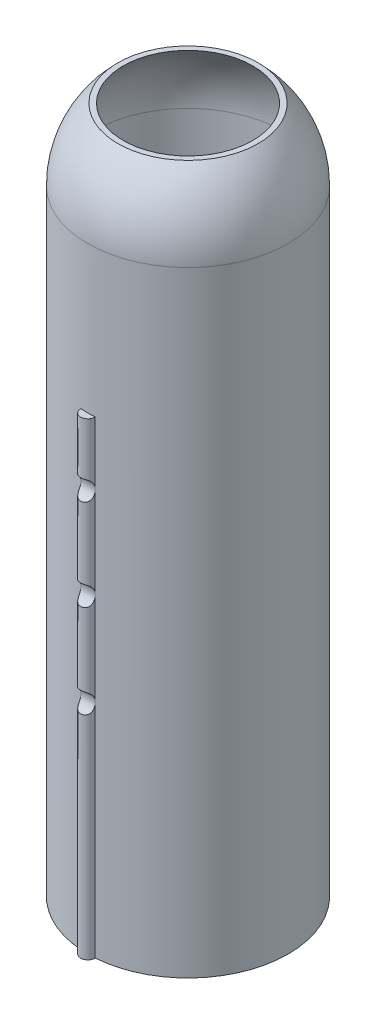
SolidWorks part; units mm, degrees
ref_plane "Front Plane" through (0, 0, 0) normal (0, 0, 1) x (1, 0, 0)
ref_plane "Top Plane" through (0, 0, 0) normal (0, 1, 0) x (1, 0, 0)
ref_plane "Right Plane" through (0, 0, 0) normal (1, 0, 0) x (0, 0, -1)
sketch "Sketch3" plane through (0, 0, 0) normal (0, 1, 0) x (1, 0, 0)
  line L0 (-117.7273, 0) -> (58.3627, 0) construction
  circle A0 centre (0, 0) radius 42.0688
  circle A1 centre (0, 0) radius 44.45
  circle A2 centre (0, 0) radius 47.625
  arc A3 (3.173, 44.3366) -> (-3.173, 44.3366) centre (0, 44.45) ccw
  arc A4 (-3.173, -44.3366) -> (3.173, -44.3366) centre (0, -44.45) ccw
  dimension "D1" = 84.1375
  dimension "D3" = 95.25
extrude "Boss-Extrude1" add sketch "Sketch3" along normal blind 273.05 contours L0 A1 A0 | A1 L0 A0 region at (0, 0, -43.0627) region at (43.2594, 0, 0.9939)
extrude "Boss-Extrude2" add sketch "Sketch3<3>" along normal blind 207.9625 contours A1 A3 | A4 A1 region at (0, 0, -45.7769) region at (0, 0, 45.7769)
sketch "Sketch3<3>" plane through (0, 0, 0) normal (0, 1, 0) x (1, 0, 0) same geometry as "Sketch3"
sketch "Sketch5" plane through (0, 0, 0) normal (-1, 0, 0) x (0, 0, 1)
  line L0 (0, -1000) -> (0, 49000) construction
  line L1 (-44.3366, 0) -> (44.3366, 0) construction
  line L2 (-1045.8385, 0) -> (48954.1615, 0) construction
  line L3 (-44.3366, 207.9625) -> (-44.3366, 0) construction
  circle A0 centre (-49.0991, 98.425) radius 4.7625
  circle A1 centre (-49.0991, 139.7) radius 4.7625
  circle A2 centre (-49.0991, 180.1812) radius 4.7625
  circle A3 centre (49.0991, 180.1812) radius 4.7625
  circle A4 centre (49.0991, 139.7) radius 4.7625
  circle A5 centre (49.0991, 98.425) radius 4.7625
  point P11 (0, 0)
  dimension "D1" = 9.525
  dimension "D2" = 98.425
  dimension "D3" = 139.7
  dimension "D4" = 180.1812
extrude "Cut-Extrude3" cut sketch "Sketch5" against normal through all and the other way through all
sketch "Sketch6" plane through (0, 0, 0) normal (0, 0, 1) x (1, 0, 0)
  line L1 (44.45, 273.05) -> (-44.45, 273.05)
  line L5 (0, 273.05) -> (0, 319.7344) construction
  line L6 (-31.1085, 304.8) -> (31.1085, 304.8)
  arc A0 (44.45, 273.05) -> (31.1085, 304.8) centre (0, 273.05) ccw
  arc A1 (-44.45, 273.05) -> (-31.1085, 304.8) centre (0, 273.05) cw
  arc A2 (-42.0688, 273.05) -> (-28.7273, 304.8) centre (2.3813, 273.05) cw
  arc A3 (42.0688, 273.05) -> (28.7273, 304.8) centre (-2.3813, 273.05) ccw
  point P11 (0, 304.8)
  dimension "D1" = 44.45
  dimension "D5" = 44.45
  dimension "D6" = 44.45
  dimension "D2" = 31.75
  dimension "D3" = 2.3813
  dimension "D4" = 2.3813
  dimension "D7" = 2.3813
  dimension "D8" = 2.3813
revolve "Revolve1" add sketch "Sketch6" angle 360 about L5 region at (-43.2594, 273.4043, 0)
sketch "Sketch7" plane through (0, 0, 0) normal (1, 0, 0) x (0, 0, -1)
  line L0 (-44.3366, 0) -> (44.3366, 0) construction
  line L2 (44.45, 207.9625) -> (44.45, 273.05) construction
  circle A0 centre (0, 249.2375) radius 3.9688
  dimension "D2" = 7.9375
  dimension "D4" = 44.45
  dimension "D1" = 249.2375
extrude "Cut-Extrude4" cut sketch "Sketch7" against normal through all
